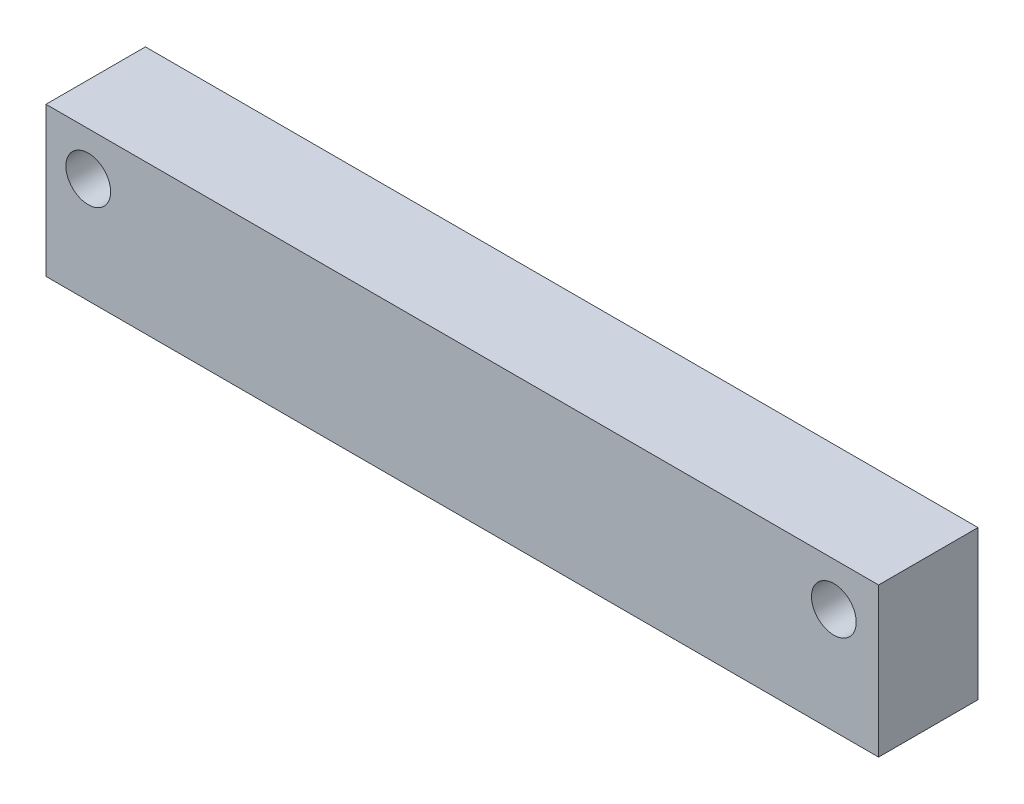
SolidWorks part; units mm, degrees
ref_plane "Front Plane" through (0, 0, 0) normal (0, 0, 1) x (1, 0, 0)
ref_plane "Top Plane" through (0, 0, 0) normal (0, 1, 0) x (1, 0, 0)
ref_plane "Right Plane" through (0, 0, 0) normal (1, 0, 0) x (0, 0, -1)
sketch "Sketch2" plane through (0, 0, 0) normal (0, 0, 1) x (1, 0, 0)
  line L0 (121.05, 58.4) -> (121.05, 32.9268) construction
  line L1 (80.65, 32.9268) -> (80.65, 58.4) construction
  line L2 (121.05, 58.4) -> (121.05, 32.9268)
  line L3 (80.65, 32.9268) -> (80.65, 58.4)
  line L4 (67.35, 50.5) -> (67.35, 38.5)
  line L5 (67.35, 38.5) -> (134.35, 38.5)
  line L6 (134.35, 38.5) -> (134.35, 50.5)
  line L7 (134.35, 50.5) -> (67.35, 50.5)
  line L8 (100.85, 50.5) -> (100.85, 38.5) construction
  line L9 (80.65, 45.6634) -> (121.05, 45.6634) construction
  line L10 (70.75, 48.5) -> (70.75, 40.5) construction
  circle A0 centre (70.75, 47) radius 1.5 construction
  circle A1 centre (70.75, 42) radius 1.5 construction
  point P12 (100.85, 45.6634)
  point P20 (70.75, 44.5)
  point P21 (100.85, 44.5)
  dimension "D1" = 12
  dimension "D2" = 67
extrude "Boss-Extrude1" add sketch "Sketch2" along normal up to surface (8 mm away) contours L3 L7 L4 L5 | L2 L7 L3 L5 | L6 L7 L2 L5 region at (127.7, 44.5, 0) region at (100.85, 44.5, 0) region at (74, 44.5, 0)
hole_wizard "M3 Clearance Hole1" positions "Sketch5" profile "Sketch4" hole size "M3" standard "ANSI Metric" end condition through all
sketch "Sketch5" plane through (0, 0, 8) normal (0, 0, 1) x (1, 0, 0)
  point P0 (70.75, 47)
  point P12 (130.75, 47)
sketch "Sketch4" plane through (70.75, 47, 8) normal (1, 0, 0) x (0, -1, 0)
  line L0 (0, 0) -> (0, 8)
  line L1 (0, 8) -> (1.8, 8)
  line L2 (1.8, 8) -> (1.8, 0)
  line L5 (1.8, 0) -> (0, 0)
  line L11 (0, -6.35) -> (0, 107.95) construction
  dimension "Thru Hole Dia." = 3.6
  dimension "Thru Hole Depth" = 8
